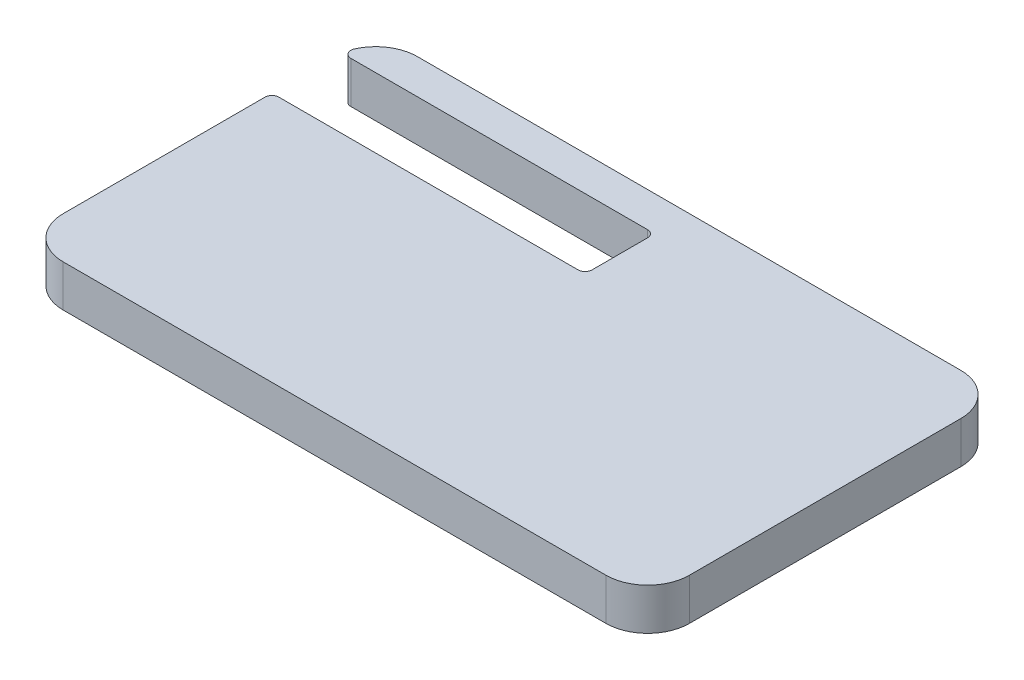
SolidWorks part; units mm, degrees
ref_plane "Alzado" through (0, 0, 0) normal (0, 0, 1) x (1, 0, 0)
ref_plane "Planta" through (0, 0, 0) normal (0, 1, 0) x (1, 0, 0)
ref_plane "Vista lateral" through (0, 0, 0) normal (1, 0, 0) x (0, 0, -1)
sketch "Croquis1" plane through (0, 0, 0) normal (0, 1, 0) x (1, 0, 0)
  line L5 (-22.5, 9.9298) -> (22.5, 9.9298)
  line L6 (-22.5, 9.9298) -> (-22.5, -15.5702)
  line L7 (-22.5, -15.5702) -> (22.5, -15.5702)
  line L8 (22.5, 9.9298) -> (22.5, -15.5702)
  dimension "D1" = 9.9298
  dimension "D2" = 22.5
  dimension "D3" = 25.5
  dimension "D4" = 45
extrude "Saliente-Extruir1" add sketch "Croquis1" along normal blind 3
sketch "Croquis2" plane through (0, 3, 0) normal (0, 1, 0) x (1, 0, 0)
  line L0 (-22.5, 9.9298) -> (-22.5, -15.5702) construction
  line L1 (-22.5, 7.4298) -> (0, 7.4298)
  line L2 (-22.5, 7.4298) -> (-22.5, 2.4298)
  line L3 (-22.5, 2.4298) -> (0, 2.4298)
  line L4 (0, 7.4298) -> (0, 2.4298)
  line L6 (22.5, 9.9298) -> (-22.5, 9.9298) construction
  dimension "D1" = 22.5
  dimension "D2" = 2.5
  dimension "D3" = 5
extrude "Cortar-Extruir1" cut sketch "Croquis2" against normal up to surface (3 mm away) up to face at (0, 0, 2.8202)
fillet "Redondeo1" radius 3 4 edges at (-22.5, 1.5, 15.5702) (-22.5, 1.5, -9.9298) (22.5, 1.5, 15.5702) (22.5, 1.5, -9.9298)
fillet "Redondeo4" radius 0.5 4 edges at (-22.5, 1.5, -2.4298) (0, 1.5, -2.4298) (0, 1.5, -7.4298) (-22.5, 1.5, -7.4298)
